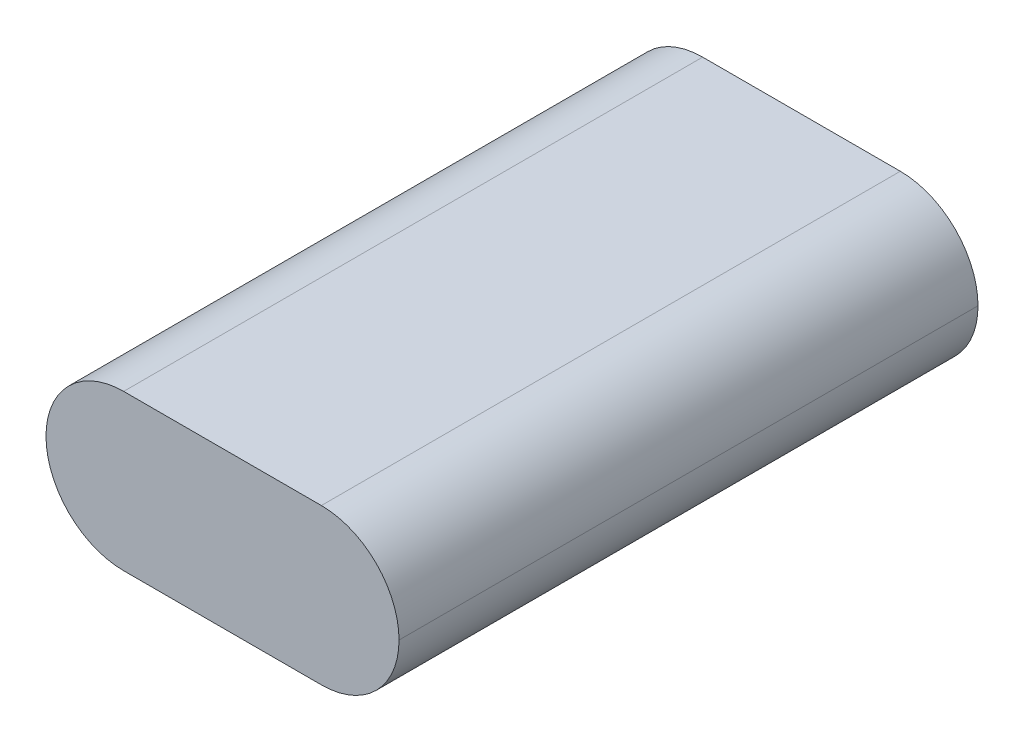
SolidWorks part; units mm, degrees
ref_plane "Piano frontale" through (0, 0, 0) normal (0, 0, 1) x (1, 0, 0)
ref_plane "Piano superiore" through (0, 0, 0) normal (0, 1, 0) x (1, 0, 0)
ref_plane "Piano destro" through (0, 0, 0) normal (1, 0, 0) x (0, 0, -1)
sketch "Schizzo1" plane through (0, 0, 0) normal (0, 1, 0) x (1, 0, 0)
  line L1 (0, 0) -> (-25, 0)
  line L2 (0, 0) -> (0, 41)
  line L3 (0, 41) -> (-25, 41)
  line L4 (-25, 0) -> (-25, 41)
  dimension "D1" = 25
  dimension "D2" = 41
extrude "Estrusione-Estrusione1" add sketch "Schizzo1" along normal blind 11
fillet "Raccordo1" radius 5.5 4 edges at (-25, 11, -20.5) (-25, 0, -20.5) (0, 0, -20.5) (0, 11, -20.5)
